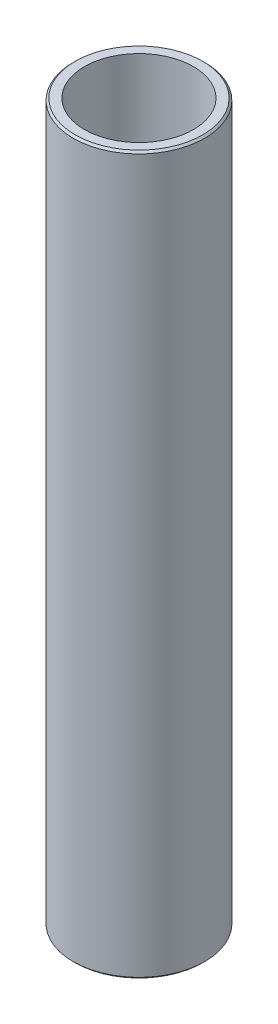
SolidWorks part; units mm, degrees
ref_plane "Front Plane" through (0, 0, 0) normal (0, 0, 1) x (1, 0, 0)
ref_plane "Top Plane" through (0, 0, 0) normal (0, 1, 0) x (1, 0, 0)
ref_plane "Right Plane" through (0, 0, 0) normal (1, 0, 0) x (0, 0, -1)
sketch "Sketch1" plane through (0, 0, 0) normal (0, 1, 0) x (1, 0, 0)
  circle A0 centre (0, 0) radius 55
  dimension "SHAFT_OD" = 110
extrude "Boss-Extrude1" add sketch "Sketch1" along normal blind 600
sketch "Sketch2" plane through (0, 0, 0) normal (0, 1, 0) x (1, 0, 0)
  circle A0 centre (0, 0) radius 45.6349
  dimension "BORE_D" = 91.2699
extrude "Cut-Extrude1" cut sketch "Sketch2" along normal through all
chamfer "Chamfer1" distance 1.6335 angle 45 2 edges at (0, 600, 55) (0, 0, 55)
